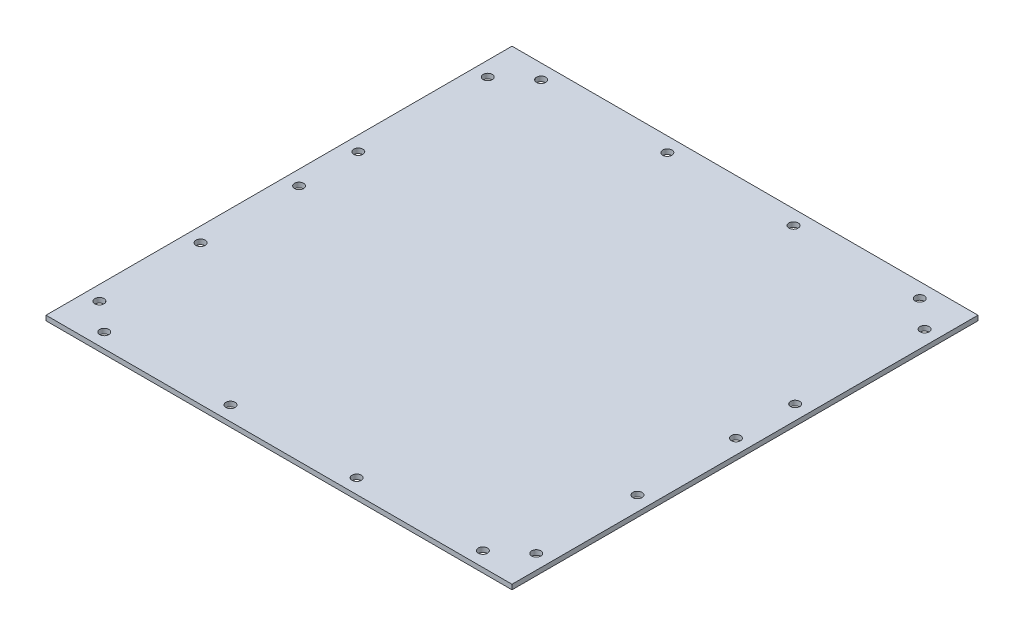
SolidWorks part; units mm, degrees
ref_plane "Front Plane" through (0, 0, 0) normal (0, 0, 1) x (1, 0, 0)
ref_plane "Top Plane" through (0, 0, 0) normal (0, 1, 0) x (1, 0, 0)
ref_plane "Right Plane" through (0, 0, 0) normal (1, 0, 0) x (0, 0, -1)
sketch "Sketch2" plane through (0, 0, 0) normal (0, 1, 0) x (1, 0, 0)
  line L0 (0, 0) -> (152.4, 0)
  line L1 (152.4, 0) -> (152.4, 152.4)
  line L2 (152.4, 152.4) -> (0, 152.4)
  line L3 (0, 152.4) -> (0, 0)
  dimension "D1" = 152.4
  dimension "D2" = 152.4
extrude "Boss-Extrude1" add sketch "Sketch2" along normal blind 1.5875
sketch "Sketch3" plane through (0, 1.5875, 0) normal (0, 1, 0) x (1, 0, 0)
  line L0 (0, 152.4) -> (4.7625, 152.4)
  line L1 (152.4, 152.4) -> (0, 152.4) construction
  line L2 (4.7625, 152.4) -> (4.7625, 0)
  line L3 (0, 0) -> (152.4, 0) construction
  line L4 (0, 152.4) -> (0, 147.6375)
  line L5 (0, 152.4) -> (0, 0) construction
  line L6 (0, 147.6375) -> (152.4, 147.6375)
  line L7 (152.4, 0) -> (152.4, 152.4) construction
  line L8 (152.4, 152.4) -> (147.6375, 152.4)
  line L9 (147.6375, 152.4) -> (147.6375, 0)
  line L10 (152.4, 0) -> (152.4, 4.7625)
  line L11 (152.4, 4.7625) -> (0, 4.7625)
  point P21 (4.7625, 139.7)
  point P23 (14.2875, 147.6375)
  point P24 (147.6375, 139.7)
  point P25 (138.1125, 4.7625)
  point P26 (4.7625, 12.7)
  dimension "D1" = 4.7625
  dimension "D2" = 4.7625
  dimension "D3" = 4.7625
  dimension "D4" = 4.7625
  dimension "D5" = 12.7
  dimension "D6" = 14.2875
  dimension "D7" = 12.7
  dimension "D8" = 14.2875
  dimension "D9" = 12.7
sketch "Sketch4" plane through (0, 1.5875, 0) normal (0, 1, 0) x (1, 0, 0)
  point P0 (14.2875, 147.6375)
  point P3 (147.6375, 139.7)
  point P6 (138.1125, 4.7625)
  point P9 (4.7625, 12.7)
sketch "Sketch6" plane through (0, 1.5875, 0) normal (0, 1, 0) x (1, 0, 0)
  line L0 (152.4, 4.7625) -> (0, 4.7625) construction
  line L1 (0, 152.4) -> (0, 0) construction
  point P0 (14.2875, 147.6375)
  point P3 (14.2875, 4.7625)
  dimension "D1" = 14.2875
hole_wizard "Ø3.0mm Dowel Hole2" positions "Sketch6" profile "Sketch7" hole size "Ø3.0" standard "ANSI Metric" end condition through all
sketch "Sketch7" plane through (14.2875, 1.5875, -147.6375) normal (1, 0, 0) x (0, 0, 1)
  line L0 (0, 0) -> (0, 1.5875)
  line L1 (0, 1.5875) -> (1.5, 1.5875)
  line L2 (1.5, 1.5875) -> (1.5, 0)
  line L5 (1.5, 0) -> (0, 0)
  line L11 (0, -6.35) -> (0, 107.95) construction
  dimension "Thru Hole Dia." = 3
  dimension "Thru Hole Depth" = 1.5875
sketch "Sketch8" plane through (0, 1.5875, 0) normal (0, 1, 0) x (1, 0, 0)
  point P0 (4.7625, 139.7)
  point P3 (147.6375, 139.7)
hole_wizard "Ø3.0mm Dowel Hole3" positions "Sketch8" profile "Sketch9" hole size "Ø3.0" standard "ANSI Metric" end condition through all
sketch "Sketch9" plane through (4.7625, 1.5875, -139.7) normal (1, 0, 0) x (0, 0, 1)
  line L0 (0, 0) -> (0, 1.5875)
  line L1 (0, 1.5875) -> (1.5, 1.5875)
  line L2 (1.5, 1.5875) -> (1.5, 0)
  line L5 (1.5, 0) -> (0, 0)
  line L11 (0, -6.35) -> (0, 107.95) construction
  dimension "Thru Hole Dia." = 3
  dimension "Thru Hole Depth" = 1.5875
pattern_linear "LPattern1" count 4 spacing 42.3333 along (0, 0, 1) skipping (2, 0) of "Ø3.0mm Dowel Hole3"
pattern_linear "LPattern2" count 4 spacing 41.275 along (1, 0, 0) of "Ø3.0mm Dowel Hole2"
sketch "Sketch10" plane through (0, 1.5875, 0) normal (0, 1, 0) x (1, 0, 0)
  line L1 (0, 0) -> (152.4, 0) construction
  point P1 (147.6375, 45.79)
  point P3 (0, 0)
  point P5 (147.6375, 78)
  point P6 (0, 0)
  point P7 (0, 0)
  point P8 (0, 0)
  point P9 (0, 0)
  dimension "D1" = 32.21
  dimension "D2" = 78
hole_wizard "Ø3.0mm Dowel Hole1" positions "Sketch10" profile "Sketch11" hole size "Ø3.0" standard "ANSI Metric" end condition through all
sketch "Sketch11" plane through (147.6375, 1.5875, -45.79) normal (1, 0, 0) x (0, 0, 1)
  line L0 (0, 0) -> (0, 1.5875)
  line L1 (0, 1.5875) -> (1.5, 1.5875)
  line L2 (1.5, 1.5875) -> (1.5, 0)
  line L5 (1.5, 0) -> (0, 0)
  line L11 (0, -6.35) -> (0, 107.95) construction
  dimension "Thru Hole Dia." = 3
  dimension "Thru Hole Depth" = 1.5875
ref_plane "Plane1" through (76.2, 0, 0) normal (1, 0, 0) x (0, 0, -1)
mirror "Mirror1" about plane through (76.2, 0, 0) normal (1, 0, 0) of "Ø3.0mm Dowel Hole1"
